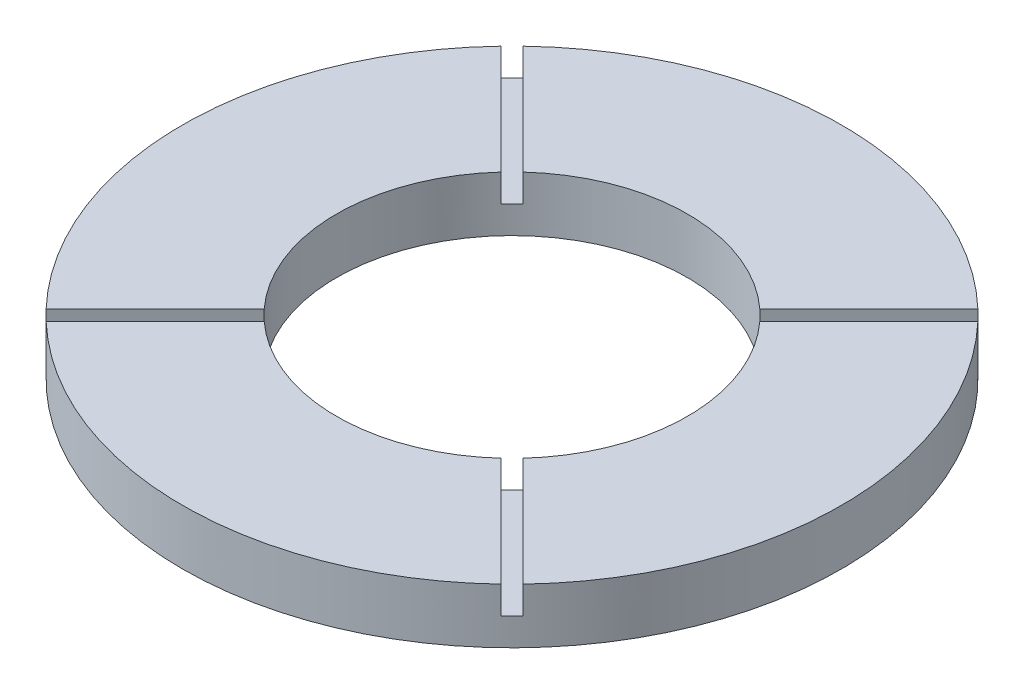
SolidWorks part; units mm, degrees
ref_plane "Front Plane" through (0, 0, 0) normal (0, 0, 1) x (1, 0, 0)
ref_plane "Top Plane" through (0, 0, 0) normal (0, 1, 0) x (1, 0, 0)
ref_plane "Right Plane" through (0, 0, 0) normal (1, 0, 0) x (0, 0, -1)
sketch "Sketch1" plane through (0, 0, 0) normal (0, 1, 0) x (1, 0, 0)
  circle A0 centre (0, 0) radius 40.4114
  circle A1 centre (0, 0) radius 75.9206
  dimension "D1" = 80.8228
  dimension "D2" = 151.8412
extrude "Boss-Extrude1" add sketch "Sketch1" along normal blind 12.7 contours A1
extrude "Cut-Extrude2" cut sketch "Sketch1<10>" along normal through all contours A0
sketch "Sketch1<10>" plane through (0, 0, 0) normal (0, 1, 0) x (1, 0, 0) same geometry as "Sketch1"
sketch "Sketch2" plane through (0, 12.7, 0) normal (0, 1, 0) x (1, 0, 0)
  line L1 (0, 0) -> (75.9206, 0)
  circle A1 centre (0, 0) radius 75.9206 construction
  circle A2 centre (0, 0) radius 75.9206
  circle A3 centre (75.9206, 0) radius 12.7
  circle M4 centre (0, 0) radius 75.9206
  dimension "D1" = 25.4
extrude "Cut-Extrude3" [suppressed] cut sketch "Sketch2" against normal through all contours A3 L1 M4 | L1 A3 M4
sketch "Sketch3" plane through (0, 12.7, 0) normal (0, 1, 0) x (1, 0, 0)
  line L2 (0, 0) -> (-64.4052, 64.4052) construction
  line L7 (-28.18, 25.7015) -> (-25.7015, 28.18)
  line L8 (-28.18, 25.7015) -> (-63.0053, 60.5267)
  line L19 (0, 0) -> (0, 89.3827) construction
  line L20 (-25.7015, 28.18) -> (-60.5267, 63.0053)
  line L21 (-63.0053, 60.5267) -> (-60.5267, 63.0053)
  line L22 (-28.18, 25.7015) -> (-60.5267, 63.0053) construction
  line L23 (-25.7015, 28.18) -> (-63.0053, 60.5267) construction
  line L24 (28.18, 25.7015) -> (63.0053, 60.5267)
  line L25 (25.7015, 28.18) -> (28.18, 25.7015)
  line L26 (25.7015, 28.18) -> (60.5267, 63.0053)
  line L27 (60.5267, 63.0053) -> (63.0053, 60.5267)
  line L28 (25.7015, -28.18) -> (60.5267, -63.0053)
  line L29 (28.18, -25.7015) -> (25.7015, -28.18)
  line L30 (28.18, -25.7015) -> (63.0053, -60.5267)
  line L31 (63.0053, -60.5267) -> (60.5267, -63.0053)
  line L32 (-28.18, -25.7015) -> (-63.0053, -60.5267)
  line L33 (-25.7015, -28.18) -> (-28.18, -25.7015)
  line L34 (-25.7015, -28.18) -> (-60.5267, -63.0053)
  line L35 (-60.5267, -63.0053) -> (-63.0053, -60.5267)
  point P0 (0, 0)
  point P4 (-44.3534, 44.3534)
  point P9 (0, 0)
  point P25 (0, 0)
  point P30 (0, 0)
  point P31 (-4.3236, 4.5408)
  dimension "D1" = 45
  dimension "D2" = 3.5052
  dimension "D3" = 38.1
  dimension "D4" = 4
ref_plane "Plane1" through (0, 6.35, 0) normal (0, 1, 0) x (1, 0, 0)
extrude "Cut-Extrude5" cut sketch "Sketch3" against normal blind 6.35
equation "\"Bodytube_OD\" = 6.17in"
equation "\"Bodytube_ID\" = 5.998in"
equation "\"Motor_OD\" = 4in"
equation "\"Fwd_Tube_Length\" = 38in"
equation "\"Mid_Tube_Length\" = 8in"
equation "\"Aft_Section_Length\"= 40in"
equation "\"Mid_Coupler_Length\" = 13in"
equation "\"Aft_Lower_Length\"= 22in"
equation "\"AB_Coupler_OD_Length\"= 1in"
equation "\"AB_Coupling_Section_Length\"= 0.375in"
equation "\"AB_Coupler_Length\"= \"AB_Coupler_OD_Length\" + \"AB_Coupling_Section_Length\" * 2"
equation "\"Cutout_Angle\" = 80"
equation "\"AB_Paddle_Height\" = 0.375in"
equation "\"AB_Coupler_Num_Screws\"= 6"
equation "\"Num_Cutouts\" = 3"
equation "\"AB_Coupler_OD\"= 6.17in"
equation "\"AB_Coupler_ID\"= 5.75in"
equation "\"AB_Coupler_Surface_Diameter\"= 5.998in"
equation "\"AB_Coupling_Screw_Diameter\"= 0.1065in"
equation "\"AB_Central_Bushing_Length\" = .75in"
equation "\"Lead_Screw_Dist\" = 2.25in"
equation "\"Lead_Screw_Diam\" = (27/64)*1in"
equation "\"Lead_Screw_Length\" = (\"Mid_Coupler_Length\" + 2*0.375in + 2*0.5in)"
equation "\"Paddle_Pin_Offset\" = .25in"
equation "\"Paddle_Pin_Radius\" = 2.25in"
equation "\"Paddle_Gear_OD\" = 3.2in"
equation "\"Fwd_BKHD_From_Top\" = 18in"
equation "\"D2@Sketch1\" = \"Bodytube_ID\" - 0.02"
equation "\"D1@Sketch1\" = 3.162 + 0.02"
equation "\"Fin_Thickness\"= .118in"
equation "\"Guiderail_Cutout_Diameter\"= 1.5in"
equation "\"D1@Sketch2\" = 1"
equation "\"D2@Sketch3\"= \"Fin_Thickness\" + 0.02"
